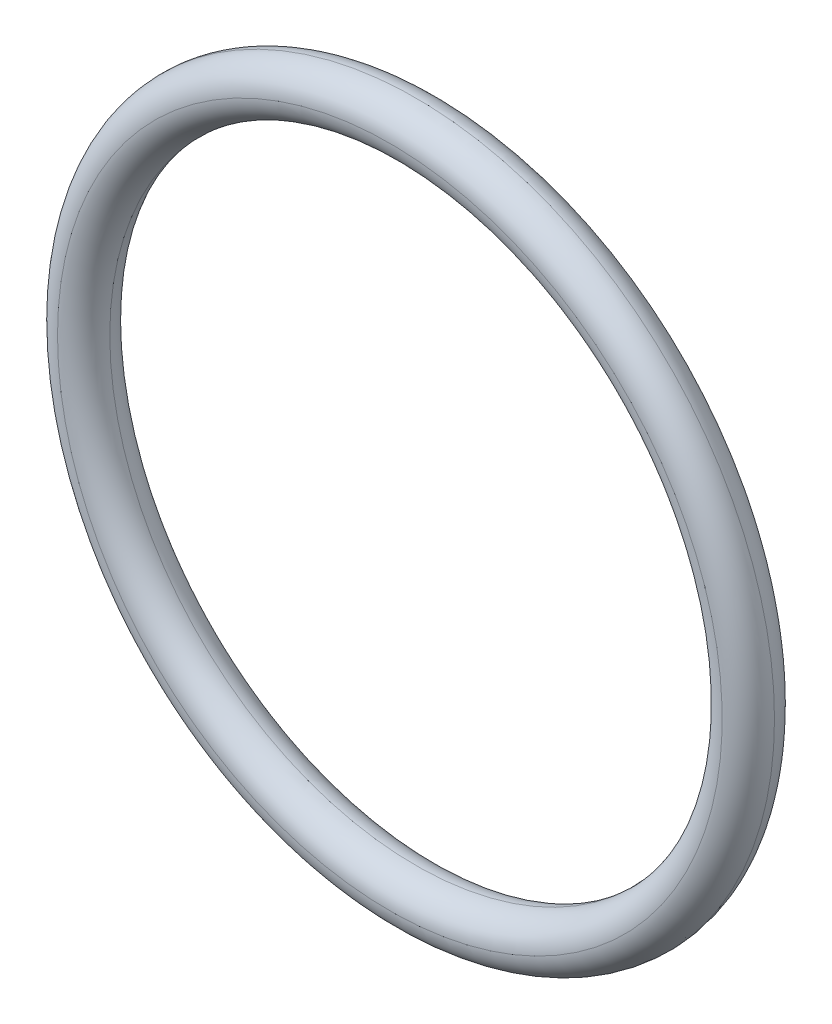
SolidWorks part; units mm, degrees
ref_plane "Front Plane" through (0, 0, 0) normal (0, 0, 1) x (1, 0, 0)
ref_plane "Top Plane" through (0, 0, 0) normal (0, 1, 0) x (1, 0, 0)
ref_plane "Right Plane" through (0, 0, 0) normal (1, 0, 0) x (0, 0, -1)
sketch "Sketch7" plane through (-0.2808, 0.4426, -13.9066) normal (0, 0, -1) x (-1, 0, 0)
  circle A1 centre (-13.808, -75.6278) radius 20.5
  circle A2 centre (-13.808, -75.6278) radius 24
  dimension "D1" = 3.5
extrude "Boss-Extrude6" add sketch "Sketch7" along normal blind 3.5
fillet "Fillet4" radius 1.75 4 edges at (-6.9728, -75.1853, -13.9066) (-6.9728, -75.1853, -17.4066) (-10.4728, -75.1853, -13.9066) (-10.4728, -75.1853, -17.4066)
